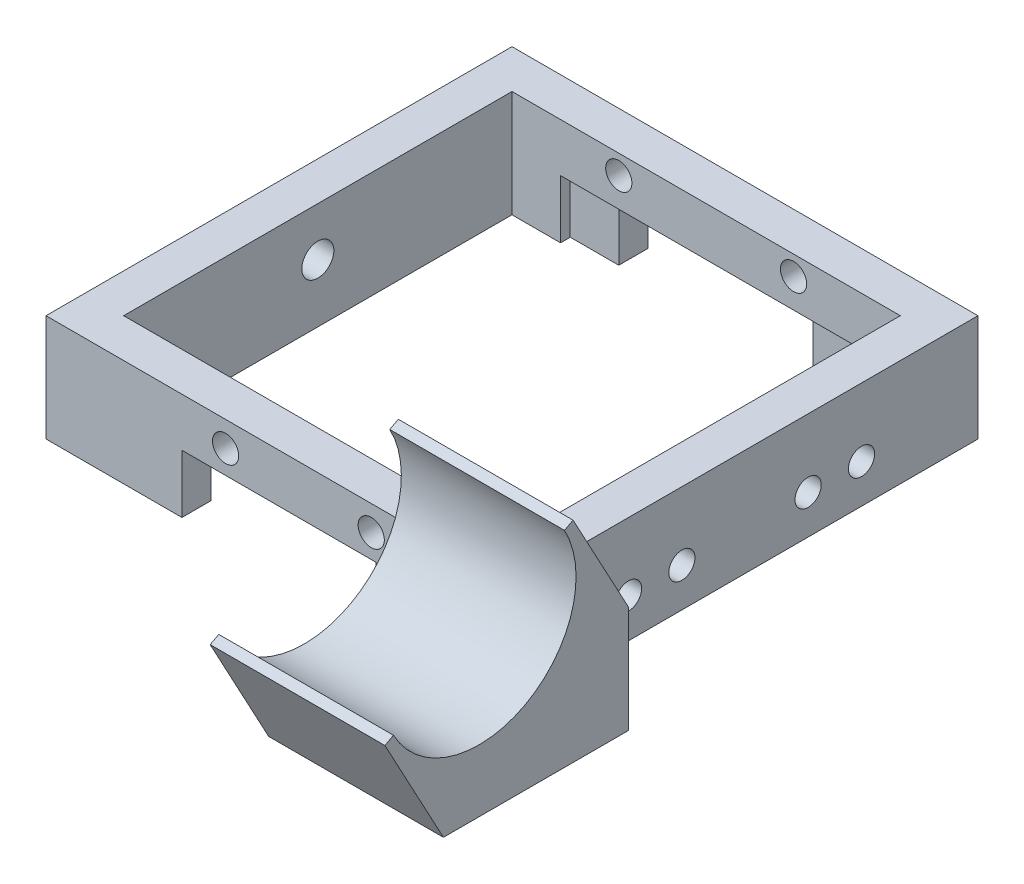
SolidWorks part; units mm, degrees
ref_plane "Front Plane" through (0, 0, 0) normal (0, 0, 1) x (1, 0, 0)
ref_plane "Top Plane" through (0, 0, 0) normal (0, 1, 0) x (1, 0, 0)
ref_plane "Right Plane" through (0, 0, 0) normal (1, 0, 0) x (0, 0, -1)
sketch "Sketch1" plane through (0, 0, 0) normal (0, 1, 0) x (1, 0, 0)
  line L0 (-20, 20) -> (20, -20) construction
  line L1 (-20, 20) -> (20, 20)
  line L2 (-20, 20) -> (-20, -20)
  line L3 (-20, -20) -> (20, -20)
  line L4 (20, 20) -> (20, -20)
  line L5 (-20, -20) -> (20, 20) construction
  line L6 (-24, 24) -> (-24, -24)
  line L7 (-24, -24) -> (24, -24)
  line L8 (24, 24) -> (24, -24)
  line L9 (-24, 24) -> (24, 24)
  point P4 (0, 0)
  dimension "D1" = 40
  dimension "D2" = 40
  dimension "D3" = 4
extrude "Boss-Extrude1" add sketch "Sketch1" along normal blind 11
sketch "Sketch3" plane through (0, 0, 24) normal (0, 0, 1) x (1, 0, 0)
  line L0 (-24, 0) -> (24, 0) construction
  line L1 (-10, 0) -> (10, 0)
  line L2 (-10, 0) -> (-10, 6)
  line L3 (-10, 6) -> (10, 6)
  line L4 (10, 0) -> (10, 6)
  point P6 (0, 6)
  dimension "D1" = 6
  dimension "D2" = 20
extrude "Cut-Extrude1" cut sketch "Sketch3" against normal through all
sketch "Sketch4" plane through (0, 0, -20) normal (0, 0, 1) x (1, 0, 0)
  line L1 (-10, 0) -> (-15, 0)
  line L2 (-10, 0) -> (-10, 6)
  line L3 (-10, 6) -> (-15, 6)
  line L4 (-15, 0) -> (-15, 6)
  line L5 (10, 0) -> (15, 0)
  line L6 (10, 0) -> (10, 6)
  line L7 (10, 6) -> (15, 6)
  line L8 (15, 0) -> (15, 6)
  dimension "D1" = 6
  dimension "D2" = 6
  dimension "D3" = 5
  dimension "D4" = 5
sketch "Sketch5" plane through (0, 0, 20) normal (0, 0, -1) x (-1, 0, 0)
  line L4 (-15, 0) -> (-10, 0)
  line L5 (-15, 6) -> (-15, 0)
  line L6 (-10, 6) -> (-15, 6)
  line L7 (-10, 0) -> (-10, 6)
  line L8 (10, 6) -> (10, 0)
  line L9 (10, 0) -> (20, 0)
  line L10 (20, 0) -> (20, 11)
  line L11 (20, 11) -> (-20, 11)
  line L12 (-20, 11) -> (-20, 0)
  line L13 (-20, 0) -> (-10, 0)
  line L14 (-10, 0) -> (-10, 6)
  line L15 (-10, 6) -> (10, 6)
  line L16 (10, 6) -> (10, 0)
  line L17 (10, 0) -> (20, 0)
  line L18 (20, 0) -> (20, 11)
  line L19 (20, 11) -> (-20, 11)
  line L20 (-20, 11) -> (-20, 0)
  line L21 (-20, 0) -> (-10, 0)
  line L22 (-10, 0) -> (-10, 6)
  line L23 (-10, 6) -> (10, 6)
  line L24 (-15, 0) -> (-10, 0)
  line L25 (-15, 6) -> (-15, 0)
  line L26 (-10, 6) -> (-15, 6)
  line L27 (-10, 0) -> (-10, 6)
  line L28 (10, 0) -> (15, 0)
  line L29 (15, 0) -> (15, 6)
  line L30 (15, 6) -> (10, 6)
  line L31 (10, 6) -> (10, 0)
  line L32 (10, 0) -> (15, 0)
  line L33 (15, 0) -> (15, 6)
  line L34 (15, 6) -> (10, 6)
  line L35 (10, 6) -> (10, 0)
  line M9 (10, 6) -> (10, 0)
  line M10 (10, 0) -> (20, 0)
  line M15 (-10, 0) -> (-10, 6)
  dimension "D1" = 0
  dimension "D2" = 0
  dimension "D3" = 0
extrude "Cut-Extrude2" cut sketch "Sketch4" against normal blind 1
extrude "Cut-Extrude3" cut sketch "Sketch5" against normal blind 1 contours L26 L25 L21 M15 | L33 L34 M9 M10 region at (12.5, 3, 20) region at (-12.5, 3, 20)
sketch "Sketch6" plane through (0, 0, -24) normal (0, 0, -1) x (-1, 0, 0)
  line L0 (-9, 9) -> (9, 9) construction
  line L1 (24, 11) -> (24, 0) construction
  line L2 (-24, 11) -> (24, 11) construction
  circle A0 centre (-9, 9) radius 1.35
  circle A1 centre (9, 9) radius 1.35
  point P4 (0, 9)
  dimension "D3" = 2.7
  dimension "D4" = 2.7
  dimension "D1" = 15
  dimension "D2" = 2
extrude "Cut-Extrude4" cut sketch "Sketch6" against normal up to next
sketch "Sketch7" plane through (0, 0, 24) normal (0, 0, 1) x (1, 0, 0)
  line L0 (24, 11) -> (24, 0) construction
  circle A0 centre (9.5, 8.4128) radius 1.35
  circle A1 centre (-5.5, 8.4128) radius 1.35
  dimension "D1" = 2.7
  dimension "D2" = 2.7
  dimension "D3" = 14.5
  dimension "D4" = 15
extrude "Cut-Extrude5" cut sketch "Sketch7" against normal up to next
sketch "Sketch8" plane through (24, 0, 0) normal (1, 0, 0) x (0, 0, -1)
  line L0 (-24, 11) -> (-24, 0) construction
  line L1 (-24, 0) -> (24, 0) construction
  line L2 (0, 0) -> (0, 11) construction
  line L3 (-24, 11) -> (24, 11) construction
  circle A0 centre (-12, 4) radius 1.35
  circle A1 centre (-6.5, 4) radius 1.35
  circle A2 centre (6.5, 4) radius 1.35
  circle A3 centre (12, 4) radius 1.35
  dimension "D3" = 2.7
  dimension "D4" = 2.7
  dimension "D1" = 12
  dimension "D2" = 5.5
  dimension "D5" = 4
extrude "Cut-Extrude6" cut sketch "Sketch8" against normal up to next
sketch "Sketch9" plane through (-24, 0, 0) normal (-1, 0, 0) x (0, 0, 1)
  line L0 (-24, 0) -> (24, 0) construction
  circle A0 centre (0, 6) radius 1.65
  dimension "D2" = 3.3
  dimension "D1" = 6
extrude "Cut-Extrude7" cut sketch "Sketch9" against normal up to next
sketch "Sketch10" plane through (24, 0, 0) normal (1, 0, 0) x (0, 0, -1)
  line L3 (-20, 0) -> (-39.064, 0)
  line L6 (-24, 0) -> (24, 0) construction
  line L7 (-20, 0) -> (-20, 11)
  line L8 (-20, 11) -> (20, 11) construction
  line L9 (-20, 11) -> (20, 11) construction
  line L12 (-20, 11) -> (-25.7118, 21.6223)
  line L13 (-39.064, 0) -> (-45.0882, 11.2033)
  line L14 (-45.0882, 11.2033) -> (-44.2074, 11.6769)
  line L15 (-26.5926, 21.1487) -> (-25.7118, 21.6223)
  circle A0 centre (-35.4, 16.4128) radius 8.5 construction
  arc A2 (-44.2074, 11.6769) -> (-26.5926, 21.1487) centre (-35.4, 16.4128) ccw
  arc A3 (-45.0882, 11.2033) -> (-25.7118, 21.6223) centre (-35.4, 16.4128) ccw
  point P9 (0, 0)
  point P10 (-41.0516, 8.163)
  point P13 (-40.7824, 6.8196)
  point P16 (-45.2684, 11.5534)
  line M6 (-24, 0) -> (24, 0)
  line M8 (24, 11) -> (-24, 11)
  line M9 (-24, 11) -> (-24, 0)
  dimension "D2" = 17
  dimension "D1" = 20
  dimension "D3" = 22
extrude "Boss-Extrude7" add sketch "Sketch10" along normal blind 8 and the other way blind 10 contours A3 L13 L3 L12 M9 M8 | L14 A3 L15 A2 | L7 M6 M8 M9 region at (24, 5.5, 22) region at (24, 5.427, 30.4122) region at (24, 6.9561, 30.315)
